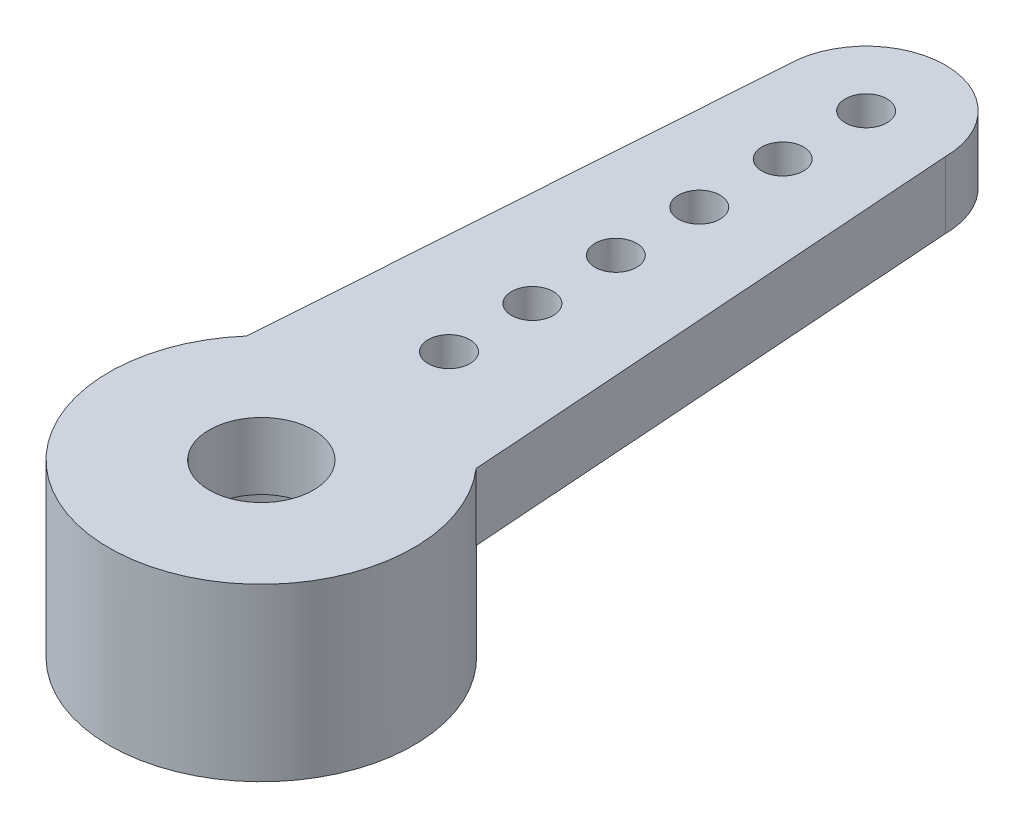
SolidWorks part; units mm, degrees
ref_plane "Front Plane" through (0, 0, 0) normal (0, 0, 1) x (1, 0, 0)
ref_plane "Top Plane" through (0, 0, 0) normal (0, 1, 0) x (1, 0, 0)
ref_plane "Right Plane" through (0, 0, 0) normal (1, 0, 0) x (0, 0, -1)
sketch "Sketch1" plane through (0, 0, 0) normal (0, 1, 0) x (1, 0, 0)
  circle A0 centre (0, 0) radius 2.5
  circle A1 centre (0, 0) radius 3.65
  dimension "D1" = 5
  dimension "D2" = 7.3
extrude "Boss-Extrude1" add sketch "Sketch1" along normal blind 2.5
sketch "Sketch2" plane through (0, 2.5, 0) normal (0, 1, 0) x (1, 0, 0)
  line L0 (0, 0) -> (0, 14.5) construction
  line L10 (-2.75, 2.4) -> (-1.9, 14.5)
  line L11 (1.9, 14.5) -> (2.75, 2.4)
  circle A5 centre (0, 0) radius 1.25
  circle A6 centre (0, 0) radius 3.65 construction
  arc A7 (-2.75, 2.4) -> (2.75, 2.4) centre (0, 0) ccw
  arc A8 (-1.9, 14.5) -> (1.9, 14.5) centre (0, 14.5) cw
  point P6 (0, 0)
  point P9 (0, 0)
  dimension "D1" = 2.5
  dimension "D4" = 5.5
  dimension "D3" = 1.9
  dimension "D2" = 14.5
extrude "Boss-Extrude2" add sketch "Sketch2" along normal blind 1.6
sketch "Sketch3" plane through (0, 4.1, 0) normal (0, 1, 0) x (1, 0, 0)
  line L0 (0, 0) -> (0, 14.5) construction
  circle A0 centre (0, 12.5) radius 0.5
  circle A1 centre (0, 10.5) radius 0.5
  circle A2 centre (0, 14.5) radius 0.5
  circle A4 centre (0, 8.5) radius 0.5
  circle A5 centre (0, 6.5) radius 0.5
  circle A6 centre (0, 4.5) radius 0.5
  point P8 (0, 0)
  point P15 (0, 0)
  dimension "D3" = 1
extrude "Cut-Extrude1" cut sketch "Sketch3" against normal up to next
